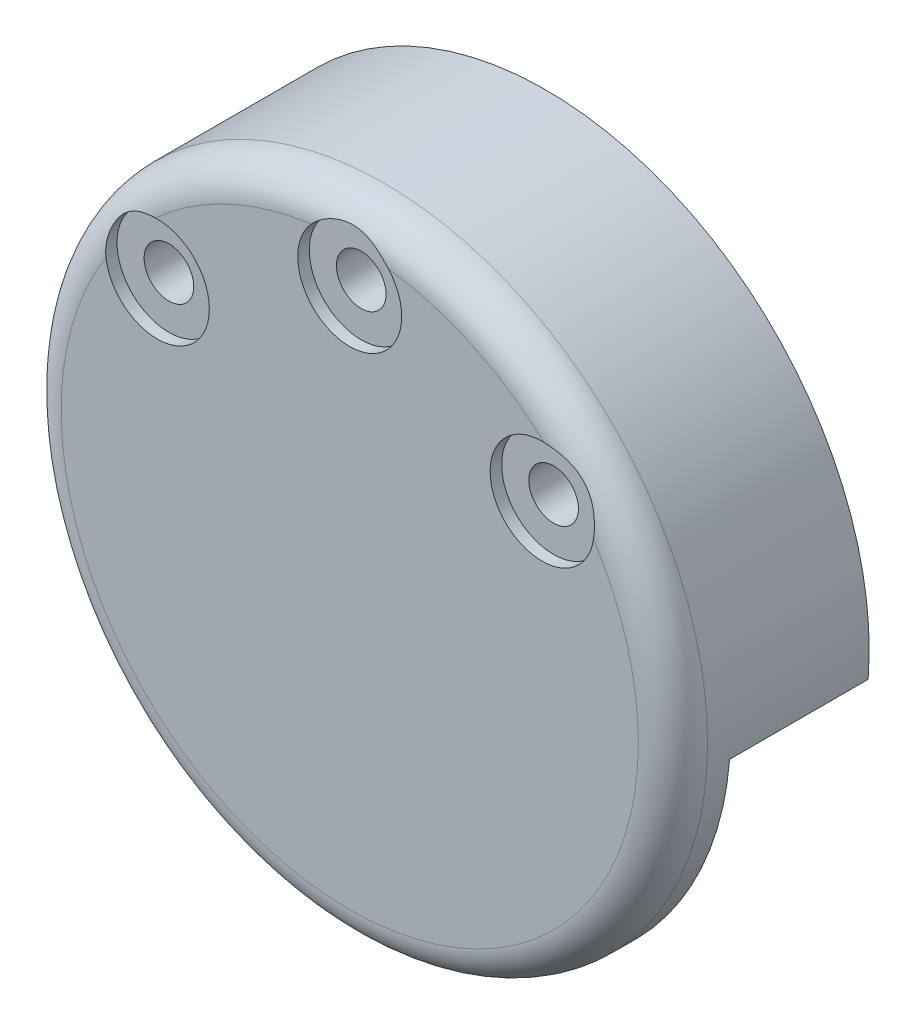
SolidWorks part; units mm, degrees
ref_plane "前视基准面" through (0, 0, 0) normal (0, 0, 1) x (1, 0, 0)
ref_plane "上视基准面" through (0, 0, 0) normal (0, 1, 0) x (1, 0, 0)
ref_plane "右视基准面" through (0, 0, 0) normal (1, 0, 0) x (0, 0, -1)
sketch "草图1" plane through (0, 0, 0) normal (0, 0, 1) x (1, 0, 0)
  circle A3 centre (0, 0) radius 28
extrude "凸台-拉伸1" add sketch "草图1" along normal blind 15
sketch "草图2" plane through (0, 0, 15) normal (0, 0, 1) x (1, 0, 0)
  line L15 (14.9965, -0.0003) -> (14.9965, -2.2623)
  line L16 (-13.6741, 6.1576) -> (-27.3145, 6.1576)
  line L17 (14.9965, -2.2623) -> (27.9085, -2.2623)
  arc A1 (-27.3145, 6.1576) -> (27.9085, -2.2623) centre (0, 0) ccw
  arc A13 (14.9965, -0.0003) -> (-13.6741, 6.1576) centre (0, 0) ccw
extrude "切除-拉伸1" cut sketch "草图2" against normal blind 22
sketch "草图3" plane through (0, 0, 15) normal (0, 0, 1) x (1, 0, 0)
  circle A0 centre (0, 0) radius 28
extrude "凸台-拉伸2" add sketch "草图3" against normal blind 3 and the other way blind 2
sketch "草图4" plane through (0, 0, 12) normal (0, 0, -1) x (-1, 0, 0)
  line L3 (26.5355, 3.5355) -> (27.7759, 3.5355)
  line L5 (26.5355, -3.5355) -> (27.7759, -3.5355)
  arc A3 (27.7759, -3.5355) -> (27.7759, 3.5355) centre (0, 0) ccw
  arc A4 (26.5355, 3.5355) -> (26.5355, -3.5355) centre (23, 0) ccw
extrude "切除-拉伸2" cut sketch "草图4" against normal blind 1
sketch "草图5" plane through (0, 0, 13) normal (0, 0, -1) x (-1, 0, 0)
  circle A1 centre (23, 0) radius 4.5
extrude "切除-拉伸3" cut sketch "草图5" against normal blind 1
sketch "草图7" plane through (0, 0, 0) normal (0, 0, 1) x (1, 0, 0)
  circle A1 centre (16.6615, 13.9806) radius 2.15
  circle A2 centre (-16.6615, 13.9806) radius 2.15
  circle A3 centre (0, 21.75) radius 2.15
extrude "切除-拉伸4" cut sketch "草图7" along normal blind 18
sketch "草图9" plane through (0, 0, 17) normal (0, 0, 1) x (1, 0, 0)
  circle A0 centre (0, 21.75) radius 4.5
  circle A1 centre (16.6615, 13.9806) radius 4.5
  circle A2 centre (-16.6615, 13.9806) radius 4.5
extrude "切除-拉伸6" cut sketch "草图9" against normal blind 1
fillet "圆角5" radius 3 2 edges at (14.9965, -2.2623, 6) (28, 0, 17)
